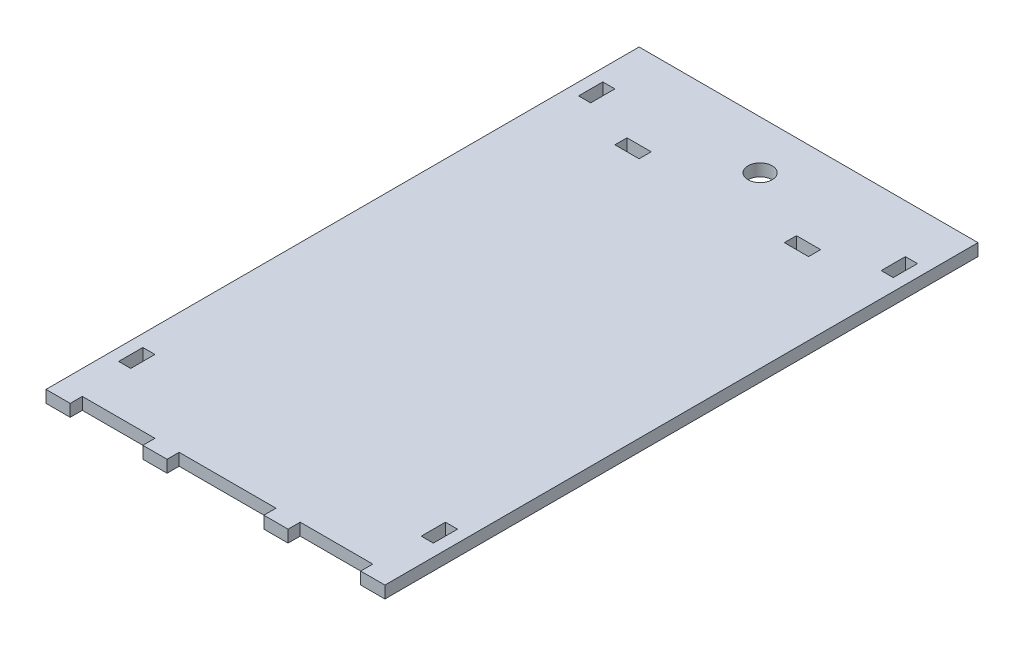
SolidWorks part; units mm, degrees
material "Beech"
ref_plane "Front Plane" through (0, 0, 0) normal (0, 0, 1) x (1, 0, 0)
ref_plane "Top Plane" through (0, 0, 0) normal (0, 1, 0) x (1, 0, 0)
ref_plane "Right Plane" through (0, 0, 0) normal (1, 0, 0) x (0, 0, -1)
sketch "Sketch1" plane through (0, 0, 0) normal (0, 1, 0) x (1, 0, 0)
  line L0 (0, 0) -> (177.8, 0)
  line L1 (0, 0) -> (0, 304.8)
  line L2 (177.8, 0) -> (177.8, 304.8)
  line L3 (0, 304.8) -> (177.8, 304.8)
  line L4 (0, 0) -> (12.7, 0)
  line L5 (0, 0) -> (0, -6.35)
  line L6 (12.7, 0) -> (12.7, -6.35)
  line L7 (0, -6.35) -> (12.7, -6.35)
  line L8 (177.8, 0) -> (165.1, 0)
  line L9 (177.8, 0) -> (177.8, -6.35)
  line L10 (165.1, 0) -> (165.1, -6.35)
  line L11 (177.8, -6.35) -> (165.1, -6.35)
  line L12 (127, 0) -> (114.3, 0)
  line L13 (127, 0) -> (127, -6.35)
  line L14 (114.3, 0) -> (114.3, -6.35)
  line L15 (127, -6.35) -> (114.3, -6.35)
  line L16 (50.8, 0) -> (63.5, 0)
  line L17 (50.8, 0) -> (50.8, -6.35)
  line L18 (63.5, 0) -> (63.5, -6.35)
  line L19 (50.8, -6.35) -> (63.5, -6.35)
  line L20 (165.1, 279.4) -> (171.45, 279.4)
  line L21 (165.1, 279.4) -> (165.1, 266.7)
  line L22 (171.45, 279.4) -> (171.45, 266.7)
  line L23 (165.1, 266.7) -> (171.45, 266.7)
  line L24 (6.35, 279.4) -> (12.7, 279.4)
  line L25 (6.35, 279.4) -> (6.35, 266.7)
  line L26 (12.7, 279.4) -> (12.7, 266.7)
  line L27 (6.35, 266.7) -> (12.7, 266.7)
  line L28 (6.35, 38.1) -> (12.7, 38.1)
  line L29 (6.35, 38.1) -> (6.35, 25.4)
  line L30 (12.7, 38.1) -> (12.7, 25.4)
  line L31 (6.35, 25.4) -> (12.7, 25.4)
  line L32 (165.1, 38.1) -> (171.45, 38.1)
  line L33 (165.1, 38.1) -> (165.1, 25.4)
  line L34 (171.45, 38.1) -> (171.45, 25.4)
  line L35 (165.1, 25.4) -> (171.45, 25.4)
  line L36 (38.1, 260.35) -> (38.1, 254)
  line L37 (38.1, 260.35) -> (50.8, 260.35)
  line L38 (38.1, 254) -> (50.8, 254)
  line L39 (50.8, 260.35) -> (50.8, 254)
  line L40 (127, 260.35) -> (127, 254)
  line L41 (127, 260.35) -> (139.7, 260.35)
  line L42 (127, 254) -> (139.7, 254)
  line L43 (139.7, 260.35) -> (139.7, 254)
  circle A0 centre (88.9, 279.4) radius 6.35
  point P21 (88.9, 304.8)
  dimension "D8" = 12.7
  dimension "D1" = 177.8
  dimension "D2" = 6.35
  dimension "D3" = 12.7
  dimension "D4" = 50.8
  dimension "D5" = 50.8
  dimension "D6" = 304.8
  dimension "D7" = 25.4
  dimension "D9" = 25.4
  dimension "D10" = 25.4
  dimension "D11" = 254
  dimension "D12" = 38.1
  dimension "D13" = 38.1
extrude "Boss-Extrude1" add sketch "Sketch1" along normal blind 6.35 contours L3 L1 L0 L2 A0 L37 L39 L38 L36 L35 L33 L32 L34 L31 L29 L28 L30 L27 L25 L24 L26 L23 L21 L20 L22 L41 L43 L42 L40 | L5 L7 L6 L0 | L17 L19 L18 L0 | L15 L13 L0 L14 | L11 L9 L0 L10 region at (88.9, 0, -151.7844) region at (6.35, 0, 3.175) region at (57.15, 0, 3.175) region at (171.45, 0, 3.175) region at (120.65, 0, 3.175)
equation "\"CageLeftBottomEdge\"=22.11mm"
equation "\"CageLeftTopEdge\"=22.11mm"
equation "\"CageRightBottomEdge\"=21.63mm"
equation "\"CageRightTopEdge\"=21.63mm"
equation "\"CageHeight\"=86.04mm"
equation "\"CageLength\"=73.76mm"
equation "\"CageTopScrewClearance\"=10mm"
equation "\"CageBottomScrewClearance\"=25mm"
equation "\"CageLeftTopDepth\"= 11.65mm"
equation "\"CageLeftBottomDepth\"=11.11mm"
equation "\"CageLeftTopHeight\"=8.56175mm"
equation "\"CageLeftBottomHeight\"=16mm"
equation "\"CageRightTopDepth\"= 11.05mm"
equation "\"CageRightBottomDepth\"=10.58mm"
equation "\"CageRightTopHeight\"=9.6mm"
equation "\"CageRightBottomHeight\"=15.49mm"
equation "\"CageLeftTopChannelDepth\"=2.41908mm"
equation "\"CageLeftBottomChannelDepth\"=2.588mm"
equation "\"CageLeftChannelHeight\"=11.7mm"
equation "\"CageRightTopChannelDepth\"=2.32mm"
equation "\"CageRightBottomChannelDepth\"=2.318mm"
equation "\"CageRightChannelHeight\"=10mm"
equation "\"CageChanRelHeight\"=23.99mm"
equation "\"CageChanRelDepth\"=5.492mm"
equation "\"CageChamberRadius\"=16.261mm"
equation "\"CageScrewDiameter\"=4.8mm"
equation "\"CageSetScrewDiameter\"=3.5mm"
equation "\"CageAxleRadius\"=6.639mm"
equation "\"CageAxleKeyHeight\"=1.619mm"
equation "\"CageAxleKeyWidth\"=2.662mm"
equation "\"CageHoseWindowWidth\"=16.29mm"
equation "\"CageHoseWindowHeight\"=26.5mm"
equation "\"CageHoseWindow-Edge\"=8.89mm"
equation "\"CageScrew-VerticalEdge\"=5.0mm"
equation "\"CageScrew-HorizontalEdge\"=7.5mm"
equation "\"CageScrew-HoseCornerScrewEdge\"=4.45mm"
equation "\"CageAxle-BottomEdge\"=56.05mm"
equation "\"CageAxle-FrontEdge\"=46.03mm"
equation "\"CageBackSetScrew-Axle\"=40mm"
equation "\"CageFrontSetScrew-Axle\"=22mm"
equation "\"CageVelocityWindow-BackEdge\"=34.8mm"
equation "\"CageVelocityWindow-BottomEdge\"=27.55mm"
equation "\"CageVelocityWindowHeight\"=22.29mm"
equation "\"CageVelocityWindowWidth\"=12.61mm"
equation "\"TriggerSlot-BottomEdge\"=6.35mm"
equation "\"TriggerSlot-FrontEdge\"=15mm"
equation "\"TriggerSlotSize\"=6.7mm"
equation "\"TriggerRackOffset\"=.236224in"
equation "\"TriggerSlotSizeInt\"=.25in"
equation "\"MotorMountLegLength\"=.25in"
equation "\"GearOffset\"=.264907in"
equation "\"TriggerSlotSpacing\"=.25in"
equation "\"TriggerMiniSlotWidth\"=3.5mm"
equation "\"TriggerRackWidth\"=6.5mm"
equation "\"TGMGearFaceDiameter\"=24.40mm"
equation "\"TGMCylinderLength\"=15.00mm"
equation "\"TGMScrewHole-Center\"=8.70mm"
equation "\"TGMScrewHoleDiameter\"=5.04mm"
equation "\"TGMCenterHoleDiameter\"=9.50mm"
equation "\"TGMShaftCollarSideLength\"=19.00mm"
equation "\"TGMShaftCollarDockingDepth\"=7.00mm"
equation "\"whitemotordepth\"=11.27mm"
equation "\"whitemotorbackdepth\"=3.845mm"
equation "\"whitemotoraxledepth\" = 3.5mm"
equation "\"whitemotoraxleoffset\"=11.4mm"
equation "\"whitemotorwidth\"=12.07mm"
equation "\"whitemotorheight\"=16.68mm"
equation "\"whitemotorcylinderlength\" =13.04mm"
equation "\"whitemotorcylinderradius\"=3.845mm"
equation "\"whitemotorcylinderoffset\"=2.35mm"
equation "\"whitemotorcutoutlength\"=1.88mm"
equation "\"whitemotorouterrad\"=5mm"
equation "\"whitemotorinnerrad\"=2.95mm"
equation "\"elasticracklength\"=2in"
equation "\"elasticrackpegsize\"=.25in"
equation "\"elasticrackpegbuffer\"=.125in"
equation "\"elasticrackpegspacing\"=1.76476378in"
equation "\"elasticbaybuffer\"=.25in"
equation "\"elasticdepth\"=.125in"
equation "\"elasticbaydepth\"=.75in"
equation "\"motormountwidth\"=12mm"
equation "\"motormountcornerfillet\"=3mm"
equation "\"pandiscradius\"=14in"
equation "\"towermaterialwidth\"=.25in"
equation "\"towerslotlength\"=.5in"
equation "\"towermarkerspace\"=5in"
equation "\"towerslothorizoffset\"=1in"
equation "\"towerslothorizspacing\"=2in"
equation "\"towerslotvertoffset\"=3in"
equation "\"towerslotvertspacing\"=2in"
equation "\"towerheight\"=12in"
equation "\"towerupslot\"=1in"
equation "\"D1@Sketch1\"=(\"towerslothorizoffset\"+\"towerslothorizspacing\"+\"towerslotlength\")*2"
equation "\"D2@Sketch1\"=\"towermaterialwidth\""
equation "\"D3@Sketch1\"=\"towerslotlength\""
equation "\"D4@Sketch1\"=\"towerslothorizspacing\""
equation "\"D5@Sketch1\"=\"towerslothorizspacing\""
equation "\"D6@Sketch1\"=\"towerheight\""
equation "\"D7@Sketch1\"=\"towerupslot\""
equation "\"toweraxle\"=.5in"
equation "\"D8@Sketch1\"=\"toweraxle\""
equation "\"D9@Sketch1\"=\"towerupslot\""
equation "\"D10@Sketch1\"= \"towerupslot\""
equation "\"D11@Sketch1\" = \"towermotorpanelheight\""
equation "\"towerplatslotoffset\"=1.5in"
equation "\"D12@Sketch1\"=\"towerplatslotoffset\""
equation "\"D13@Sketch1\"=\"towerplatslotoffset\""
equation "\"D1@Boss-Extrude1\"=\"towermaterialwidth\""
equation "\"towermotorpanelheight\"=10in"
equation "\"towerplatdepth\"=2in"
equation "\"stepperouterrad\"=10mm"
equation "\"stepperscrewsize\"=3.45mm"
equation "\"stepperscrewc2c\"=49.5mm"
equation "\"stepperdepthoffset\"=24mm"
equation "\"stepperhorizoffset\"=22.91mm"
equation "\"shaftslotOD\"=18.8mm"
equation "\"shaftslotID\"=13.28mm"
equation "\"shaftkeywidth\"=2.67mm"
equation "\"shaftkeydepth\"=1.8mm"
equation "\"shaftcollartotaldepth\"=12.5mm"
equation "\"shaftsquaredepth\"=6mm"
equation "\"shaftsetscrewsize\"=3.5mm"
equation "\"shaftkeytightdepth\"=1.85mm"
equation "\"shaftslottightID\"=12.78mm"
equation "\"shaftsetscrewoffset\"=9mm"
equation "\"cagecollartotaldepth\"=10mm"
equation "\"cagecollartotalwidth\"=35mm"
equation "\"cagecollarbasedepth\"=4mm"
